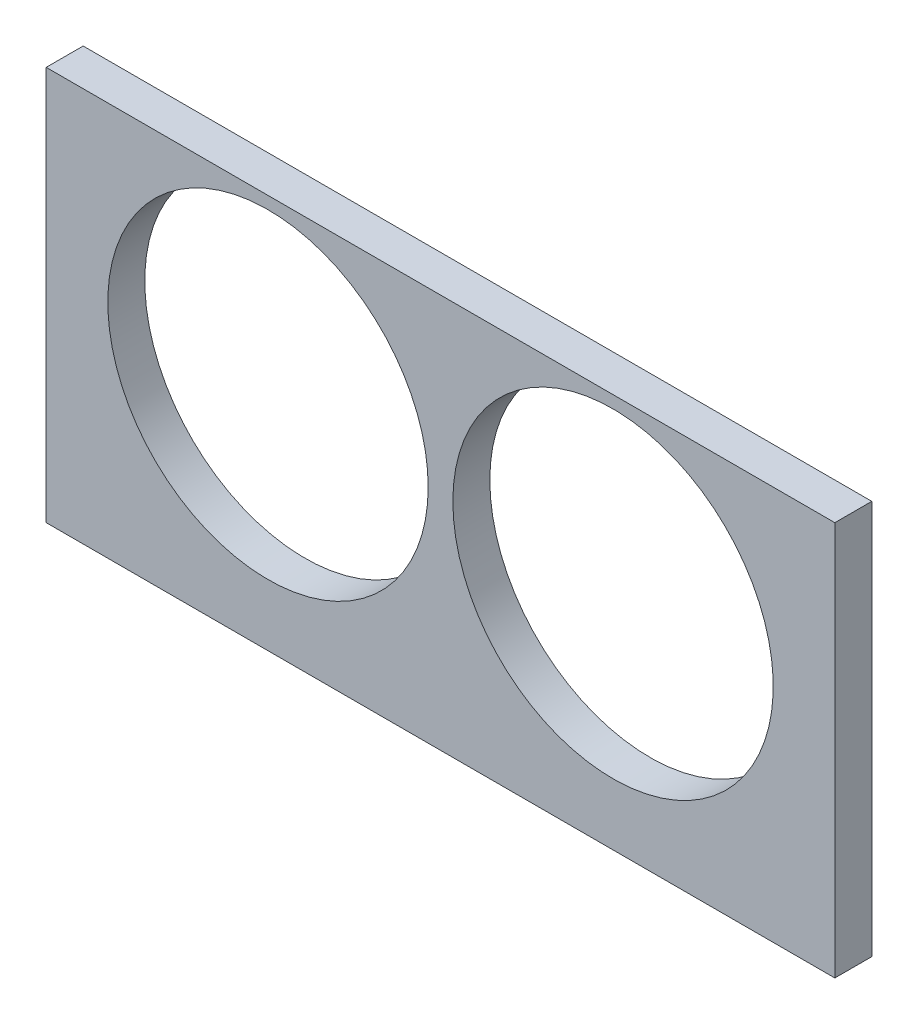
SolidWorks part; units mm, degrees
ref_plane "Front Plane" through (0, 0, 0) normal (0, 0, 1) x (1, 0, 0)
ref_plane "Top Plane" through (0, 0, 0) normal (0, 1, 0) x (1, 0, 0)
ref_plane "Right Plane" through (0, 0, 0) normal (1, 0, 0) x (0, 0, -1)
sketch "Sketch1" plane through (0, 0, 0) normal (0, 0, 1) x (1, 0, 0)
  line L0 (16, 16) -> (16, -5.1613) construction
  line L1 (0, 0) -> (32, 0)
  line L2 (0, 0) -> (0, 16)
  line L3 (0, 16) -> (32, 16)
  line L4 (32, 0) -> (32, 16)
  line L5 (0, 0) -> (32, 16) construction
  line L6 (0, 16) -> (32, 0) construction
  line L7 (0, 9) -> (32, 9) construction
  circle A0 centre (9, 9) radius 6.5
  circle A1 centre (23, 9) radius 6.5
  point P4 (16, 8)
  dimension "D1" = 13
  dimension "D2" = 7
  dimension "D3" = 9
  dimension "D4" = 32
  dimension "D5" = 16
extrude "Boss-Extrude1" add sketch "Sketch1" along normal blind 1.5
